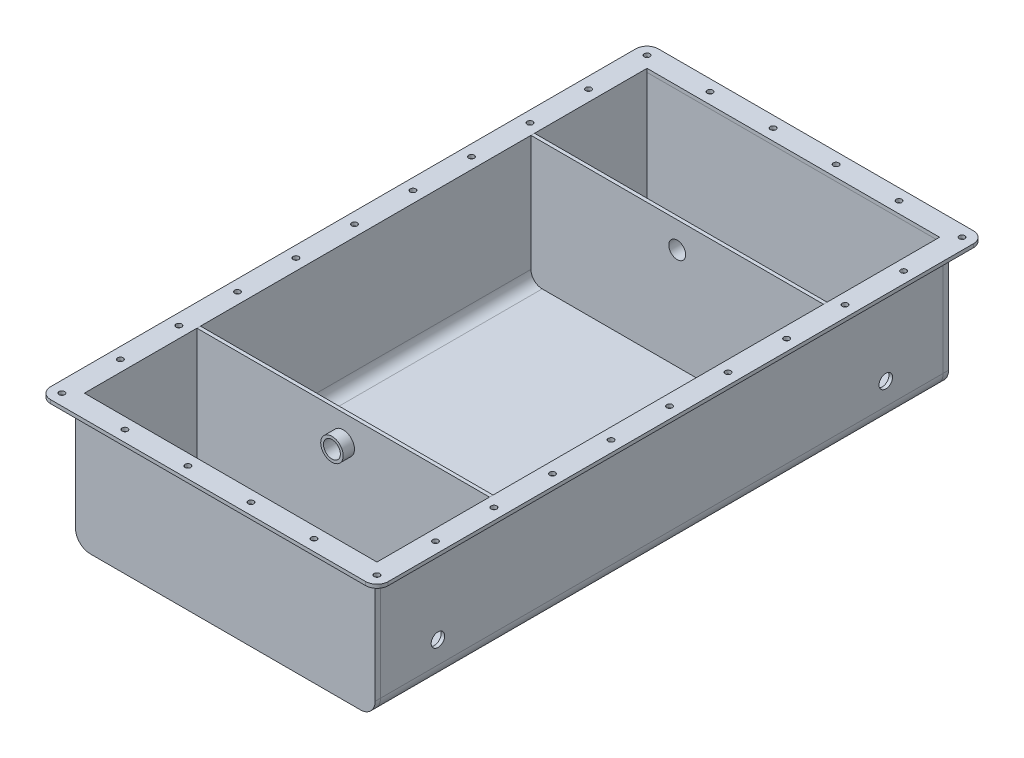
SolidWorks part; units mm, degrees
material "5052-H32"
ref_plane "Front Plane" through (0, 0, 0) normal (0, 0, 1) x (1, 0, 0)
ref_plane "Top Plane" through (0, 0, 0) normal (0, 1, 0) x (1, 0, 0)
ref_plane "Right Plane" through (0, 0, 0) normal (1, 0, 0) x (0, 0, -1)
sketch "Sketch2" plane through (0, 0, 0) normal (0, 0, 1) x (1, 0, 0)
  line L0 (-130, 0) -> (130, 0)
  line L1 (-130, 0) -> (-130, 110)
  line L2 (130, 0) -> (130, 110)
  line L3 (-133.175, -3.175) -> (-133.175, 110)
  line L4 (-133.175, -3.175) -> (133.175, -3.175)
  line L5 (133.175, -3.175) -> (133.175, 110)
  line L6 (-133.175, 110) -> (-130, 110)
  line L7 (130, 110) -> (133.175, 110)
  point P4 (0, 0)
  dimension "D1" = 260
  dimension "D3" = 110
  dimension "D4" = 110
  dimension "D2" = 3.175
  dimension "D5" = 3.175
  dimension "D6" = 3.175
extrude "Interior Dim" add sketch "Sketch2" against normal blind 500
fillet "Fillet2" radius 10 2 edges at (-130, 0, -250) (130, 0, -250)
fillet "Fillet3" radius 13.175 2 edges at (-133.175, -3.175, -250) (133.175, -3.175, -250)
ref_plane "Plane1" through (0, 0, 0) normal (0, 0, 1) x (1, 0, 0)
sketch "Sketch4" plane through (0, 0, 0) normal (0, 0, 1) x (1, 0, 0)
  line L0 (-130, 110) -> (130, 110)
  line L9 (-120, -3.175) -> (120, -3.175)
  line L10 (133.175, 10) -> (133.175, 110)
  line L11 (133.175, 110) -> (130, 110)
  line L12 (130, 110) -> (130, 10)
  line L13 (120, 0) -> (-120, 0)
  line L14 (-130, 10) -> (-130, 110)
  line L15 (-130, 110) -> (-133.175, 110)
  line L16 (-133.175, 110) -> (-133.175, 10)
  line L17 (-120, -3.175) -> (120, -3.175)
  line L18 (133.175, 10) -> (133.175, 110)
  line L19 (133.175, 110) -> (130, 110)
  line L23 (-130, 110) -> (-133.175, 110)
  line L24 (-133.175, 110) -> (-133.175, 10)
  arc A2 (120, 0) -> (130, 10) centre (120, 10) ccw
  arc A3 (-130, 10) -> (-120, 0) centre (-120, 10) ccw
  arc A13 (120, -3.175) -> (133.175, 10) centre (120, 10) ccw
  arc A14 (120, -3.175) -> (133.175, 10) centre (120, 10) ccw
  arc A16 (-133.175, 10) -> (-120, -3.175) centre (-120, 10) ccw
  arc A17 (-133.175, 10) -> (-120, -3.175) centre (-120, 10) ccw
  dimension "D1" = 0
extrude "Endcap1" add sketch "Sketch4" along normal blind 4.7625 separate body
ref_plane "Plane2" through (0, 0, -500) normal (0, 0, -1) x (-1, 0, 0)
sketch "Sketch5" plane through (0, 0, -500) normal (0, 0, -1) x (-1, 0, 0)
  line L8 (133.175, 110) -> (-133.175, 110)
  line L16 (-133.175, 110) -> (-133.175, 10)
  line L17 (-120, -3.175) -> (120, -3.175)
  line L18 (133.175, 10) -> (133.175, 110)
  line L19 (133.175, 110) -> (130, 110)
  line L20 (130, 110) -> (130, 10)
  line L21 (120, 0) -> (-120, 0)
  line L22 (-130, 10) -> (-130, 110)
  line L23 (-130, 110) -> (-133.175, 110)
  line L24 (-133.175, 110) -> (-133.175, 10)
  line L25 (-120, -3.175) -> (120, -3.175)
  line L26 (133.175, 10) -> (133.175, 110)
  arc A4 (120, 0) -> (130, 10) centre (120, 10) ccw
  arc A5 (-130, 10) -> (-120, 0) centre (-120, 10) ccw
  arc A17 (-133.175, 10) -> (-120, -3.175) centre (-120, 10) ccw
  arc A18 (-133.175, 10) -> (-120, -3.175) centre (-120, 10) ccw
  arc A19 (120, -3.175) -> (133.175, 10) centre (120, 10) ccw
  arc A20 (120, -3.175) -> (133.175, 10) centre (120, 10) ccw
  dimension "D1" = 0
ref_plane "Compartment1" through (0, 0, -100) normal (0, 0, -1) x (-1, 0, 0)
sketch "Sketch7" plane through (0, 0, -100) normal (0, 0, -1) x (-1, 0, 0)
  line L1 (130, 110) -> (-130, 110)
  line L10 (-120, -3.175) -> (120, -3.175)
  line L11 (-133.175, 110) -> (-133.175, 10)
  line L12 (-130, 110) -> (-133.175, 110)
  line L13 (-130, 10) -> (-130, 110)
  line L14 (120, 0) -> (-120, 0)
  line L15 (130, 110) -> (130, 10)
  line L16 (133.175, 110) -> (130, 110)
  line L17 (133.175, 10) -> (133.175, 110)
  line L21 (-130, 10) -> (-130, 110)
  line L22 (120, 0) -> (-120, 0)
  line L23 (130, 110) -> (130, 10)
  arc A2 (-130, 10) -> (-120, 0) centre (-120, 10) ccw
  arc A3 (-130, 10) -> (-120, 0) centre (-120, 10) ccw
  arc A6 (120, 0) -> (130, 10) centre (120, 10) ccw
  arc A7 (120, 0) -> (130, 10) centre (120, 10) ccw
  arc A12 (-133.175, 10) -> (-120, -3.175) centre (-120, 10) ccw
  arc A13 (120, -3.175) -> (133.175, 10) centre (120, 10) ccw
  dimension "D1" = 0
extrude "Compartment1_Boss" add sketch "Sketch7" along normal blind 3.175 separate body contours L22 A7 L23 L1 L21 A3 region at (0, 55.0793, -100)
ref_plane "Plane5" through (0, 110, 0) normal (0, 1, 0) x (1, 0, 0)
sketch "Sketch9" plane through (0, 110, 0) normal (0, 1, 0) x (1, 0, 0)
  line L0 (62.2463, 500) -> (-62.2463, 500) construction
  line L1 (-130, 500) -> (130, 500)
  line L2 (-130, 500) -> (-130, 0)
  line L3 (-130, 0) -> (130, 0)
  line L4 (130, 500) -> (130, 0)
  line L5 (-130, 0) -> (-130, 500) construction
  line L6 (-62.2463, 0) -> (62.2463, 0) construction
  line L7 (130, 500) -> (130, 0) construction
  line L8 (-150, 520) -> (-150, -20)
  line L9 (-150, -20) -> (150, -20)
  line L10 (150, 520) -> (150, -20)
  line L11 (-150, 520) -> (150, 520)
extrude "Lid_Flange" add sketch "Sketch9" along normal blind 3.175 separate body contours L11 L8 L9 L10 L1 L4 region at (0, 110, -513.8226)
fillet "Fillet4" radius 10 4 edges at (-150, 111.5875, -520) (150, 111.5875, -520) (150, 111.5875, 20) (-150, 111.5875, 20)
extrude "Endcap2" add sketch "Sketch5" along normal blind 4.7625 separate body
ref_plane "Compartment2" through (0, 0, -400) normal (0, 0, 1) x (1, 0, 0)
sketch "Sketch13" plane through (0, 0, -400) normal (0, 0, 1) x (1, 0, 0)
  line L0 (130, 110) -> (-130, 110)
  line L1 (133.175, 110) -> (130, 110) construction
  line L2 (130, 110) -> (130, 10) construction
  line L3 (-140, 110) -> (140, 110) construction
  line L4 (-130, 10) -> (-130, 110) construction
  line L5 (130, 110) -> (130, 10)
  line L6 (-130, 110) -> (-130, 10)
  line L7 (120, 0) -> (-120, 0)
  arc A0 (120, 0) -> (130, 10) centre (120, 10) ccw construction
  arc A1 (-130, 10) -> (-120, 0) centre (-120, 10) ccw construction
  arc A2 (-130, 10) -> (-120, 0) centre (-120, 10) ccw
  arc A3 (130, 10) -> (120, 0) centre (120, 10) cw
  dimension "D1" = 110
extrude "Compartment2_Boss" add sketch "Sketch13" along normal blind 3.175
sketch "Sketch16" plane through (-133.175, 0, 0) normal (-1, 0, 0) x (0, 0, 1)
  line L0 (-500, 0) -> (-400, 0) construction
  line L1 (-500, 110) -> (-500, 10) construction
  line L2 (0, 110) -> (0, 10) construction
  line L3 (-51, 29.5) -> (-449, 29.5) construction
  circle A0 centre (-449, 29.5) radius 6
  circle A1 centre (-51, 29.5) radius 6
  dimension "D1" = 12
  dimension "D4" = 12
  dimension "D2" = 29.5
  dimension "D3" = 51
  dimension "D5" = 51
extrude "Bearing_holes" cut sketch "Sketch16" against normal through all
sketch "Sketch17" plane through (0, 0, -400) normal (0, 0, -1) x (-1, 0, 0)
  line L0 (142.7388, 110) -> (-142.7388, 110) construction
  line L1 (130, 110) -> (130, 10) construction
  circle A0 centre (0, 90) radius 7.5
  circle A1 centre (0, 90) radius 10
  dimension "D1" = 15
  dimension "D4" = 20
  dimension "D3" = 130
extrude "Wire_Passthrough" cut sketch "Sketch17" against normal up to surface (300 mm away) contours A0 region at (0, 90, -400) up to face at (0, 39.3096, -100)
sketch "Sketch18" plane through (0, 110, 0) normal (0, 1, 0) x (1, 0, 0)
  line L1 (-130, 400) -> (130, 400)
  line L2 (-130, 400) -> (-130, 396.825)
  line L3 (-130, 396.825) -> (130, 396.825)
  line L4 (130, 400) -> (130, 396.825)
  line L5 (-130, 103.175) -> (130, 103.175)
  line L6 (-130, 103.175) -> (-130, 100)
  line L7 (-130, 100) -> (130, 100)
  line L8 (130, 103.175) -> (130, 100)
extrude "Boss-Extrude1" add sketch "Sketch18" along normal blind 3.18
extrude "Wire_Tube_2" add sketch "Sketch17<3>" along normal blind 10
sketch "Sketch17<3>" plane through (0, 0, -400) normal (0, 0, -1) x (-1, 0, 0) same geometry as "Sketch17"
sketch "Sketch19" plane through (0, 0, -100) normal (0, 0, 1) x (1, 0, 0)
  circle A0 centre (0, 90) radius 10
  circle M1 centre (0, 90) radius 7.5
  dimension "D1" = 20
extrude "Wire_Tube_1" add sketch "Sketch19" along normal blind 10 contours A0 M1 region at (-9.7172, 90, -100)
sketch "Sketch20" plane through (0, 110, 175) normal (0, 1, 0) x (1, 0, 0)
  line L0 (130, 425) -> (-130, 425) construction
  line L1 (-130, 675) -> (130, 675) construction
  line L2 (-130, 675) -> (-130, 175) construction
  line L3 (-130, 175) -> (130, 175) construction
  line L4 (130, 675) -> (130, 175) construction
  line L5 (130, 571.825) -> (130, 278.175) construction
  line L7 (0, 425) -> (0, 175) construction
  line L8 (-150, 695) -> (-150, 155) construction
  line L9 (-150, 155) -> (150, 155) construction
  line L10 (150, 695) -> (150, 155) construction
  line L11 (-150, 695) -> (150, 695) construction
  line L12 (-130, 571.825) -> (-130, 278.175) construction
  circle A0 centre (-140, 165) radius 2.5
  circle A2 centre (-140, 217) radius 2.5
  circle A3 centre (-140, 269) radius 2.5
  circle A4 centre (-140, 321) radius 2.5
  circle A5 centre (-140, 373) radius 2.5
  circle A6 centre (-140, 425) radius 2.5
  circle A7 centre (-140, 477) radius 2.5
  circle A8 centre (-140, 529) radius 2.5
  circle A9 centre (-140, 581) radius 2.5
  circle A10 centre (-140, 633) radius 2.5
  circle A16 centre (-140, 685) radius 2.5
  circle A17 centre (-84, 685) radius 2.5
  circle A18 centre (-28, 685) radius 2.5
  circle A19 centre (28, 685) radius 2.5
  circle A20 centre (84, 685) radius 2.5
  circle A21 centre (140, 685) radius 2.5
  circle A22 centre (140, 633) radius 2.5
  circle A23 centre (140, 581) radius 2.5
  circle A24 centre (140, 529) radius 2.5
  circle A25 centre (140, 477) radius 2.5
  circle A26 centre (140, 425) radius 2.5
  circle A27 centre (140, 373) radius 2.5
  circle A28 centre (140, 321) radius 2.5
  circle A29 centre (140, 269) radius 2.5
  circle A30 centre (140, 217) radius 2.5
  circle A31 centre (140, 165) radius 2.5
  circle A37 centre (84, 165) radius 2.5
  circle A38 centre (28, 165) radius 2.5
  circle A39 centre (-28, 165) radius 2.5
  circle A40 centre (-84, 165) radius 2.5
  dimension "D4" = 5
  dimension "D3" = 10
  dimension "D9" = 250
  dimension "D2" = 500
  dimension "D10" = 10
  dimension "D11" = 260
  dimension "D8" = 11
  dimension "D5" = 6
  dimension "D6" = 11
  dimension "D7" = 5
extrude "Bolt_Holes" cut sketch "Sketch20" along normal up to next
equation "\"L\" = 500"
equation "\"W\"= 260"
equation "\"D1@Sketch2\"=\"W\""
equation "\"D1@Interior Dim\" = \"L\""
equation "\"H\"= 110"
equation "\"D3@Sketch2\"=\"H\""
equation "\"D4@Sketch2\"=\"H\""
equation "\"Compartment Width\"= 100"
equation "\"D1@Compartment2\"=\"Compartment Width\""
equation "\"D1@Compartment1\"=\"Compartment Width\""
equation "\"D1@Sketch13\"=\"H\""
equation "\"D3@Sketch17\"=\"W\"/2"
equation "\"T\"= 4.7625 * 2 / 3"
equation "\"D1@Lid_Flange\"=\"T\""
equation "\"D1@Fillet3\"=\"T\"+10"
equation "\"D1@Compartment1_Boss\"=\"T\""
equation "\"D1@Compartment2_Boss\"=\"T\""
equation "\"D2@Sketch20\"=\"L\""
equation "\"D11@Sketch20\"=\"W\""
equation "\"D9@Sketch20\"=\"L\"/2"
